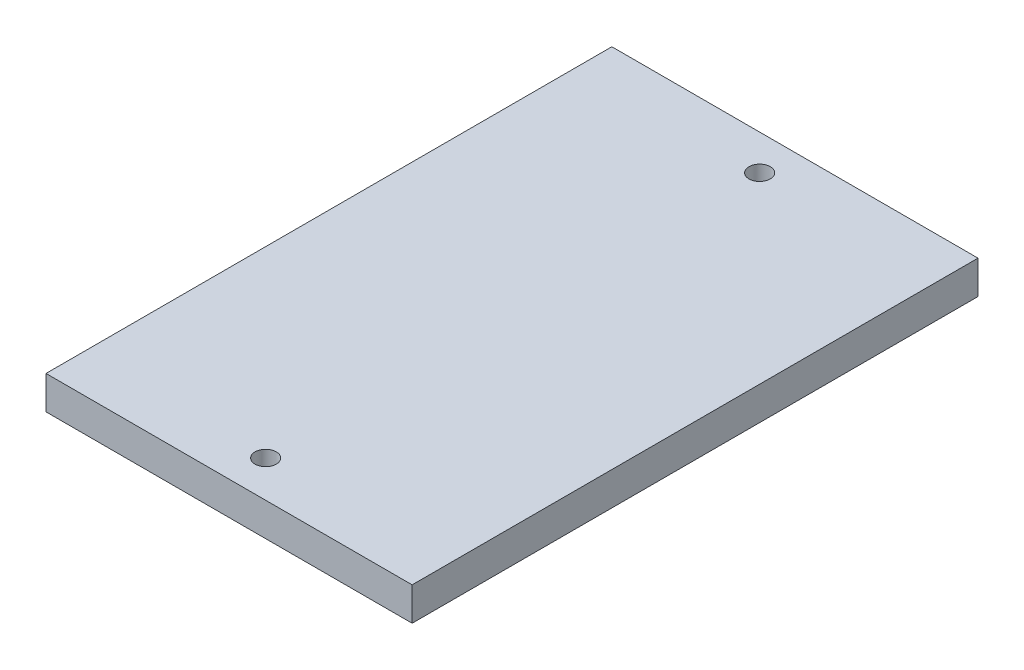
SolidWorks part; units mm, degrees
ref_plane "Front Plane" through (0, 0, 0) normal (0, 0, 1) x (1, 0, 0)
ref_plane "Top Plane" through (0, 0, 0) normal (0, 1, 0) x (1, 0, 0)
ref_plane "Right Plane" through (0, 0, 0) normal (1, 0, 0) x (0, 0, -1)
sketch "Sketch1" plane through (0, 0, 0) normal (0, 1, 0) x (1, 0, 0)
  line L1 (-27.5, -42.5) -> (27.5, -42.5)
  line L2 (-27.5, -42.5) -> (-27.5, 42.5)
  line L3 (-27.5, 42.5) -> (27.5, 42.5)
  line L4 (27.5, -42.5) -> (27.5, 42.5)
  line L5 (-27.5, -42.5) -> (27.5, 42.5) construction
  line L6 (-27.5, 42.5) -> (27.5, -42.5) construction
  circle A0 centre (0, -37) radius 1.6
  circle A1 centre (0, 37.2) radius 1.6
  point P0 (0, 0)
  dimension "D3" = 3.2
  dimension "D5" = 3.2
  dimension "D1" = 55
  dimension "D2" = 85
  dimension "D4" = 5.5
  dimension "D6" = 74.2
extrude "Boss-Extrude1" add sketch "Sketch1" along normal blind 5
equation "\"D2@Sketch1\"=85"
equation "\"D1@Sketch1\"=55"
